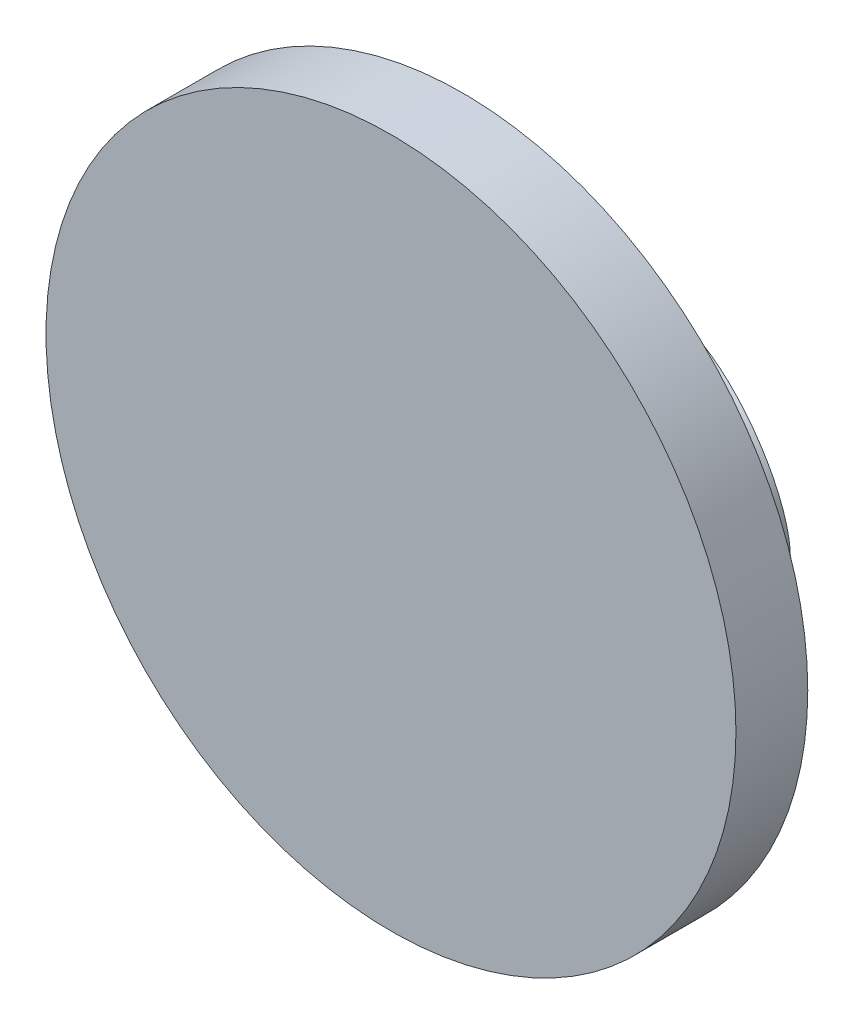
SolidWorks part; units mm, degrees
ref_plane "Front Plane" through (0, 0, 0) normal (0, 0, 1) x (1, 0, 0)
ref_plane "Top Plane" through (0, 0, 0) normal (0, 1, 0) x (1, 0, 0)
ref_plane "Right Plane" through (0, 0, 0) normal (1, 0, 0) x (0, 0, -1)
sketch "Sketch1" plane through (0, 0, 0) normal (0, 0, 1) x (1, 0, 0)
  circle A0 centre (0, 0) radius 42.5
  dimension "D1" = 85
extrude "Boss-Extrude1" add sketch "Sketch1" along normal blind 8.85
sketch "Sketch2" plane through (0, 0, 0) normal (0, 0, -1) x (-1, 0, 0)
  circle A0 centre (0, -28.4542) radius 14
  circle A1 centre (-24.642, 14.2271) radius 14
  circle A2 centre (24.642, 14.2271) radius 14
  point P9 (0, 0)
  dimension "D1" = 28
  dimension "D2" = 3
ref_axis "Axis1" through (0, 0, 8.85) along (0, 0, -1)
ref_point "Point1"
ref_axis "Axis2" through (0, -28.4542, 0) along (0, 1, 0)
ref_axis "Axis3" through (-24.642, 14.2271, 0) along (0.866, -0.5, 0)
ref_axis "Axis4" through (24.642, 14.2271, 0) along (-0.866, -0.5, 0)
ref_axis "Axis5" through (24.642, 14.2271, 0) along (-1, 0, 0)
ref_plane "Plane3" through (0, 1.6643, 4.5725) normal (0, 0.342, 0.9397) x (-1, 0, 0)
sketch "Sketch6" plane through (0, 1.6643, 4.5725) normal (0, 0.342, 0.9397) x (-1, 0, 0)
  circle A0 centre (0, 26.7382) radius 13.1557
extrude "Boss-Extrude2" add sketch "Sketch6" against normal blind 10 from offset 10 offset against normal yes
pattern_circular "CirPattern1" count 3 over 360 about axis through (0, 0, 8.85) along (0, 0, -1) of "Boss-Extrude2"
